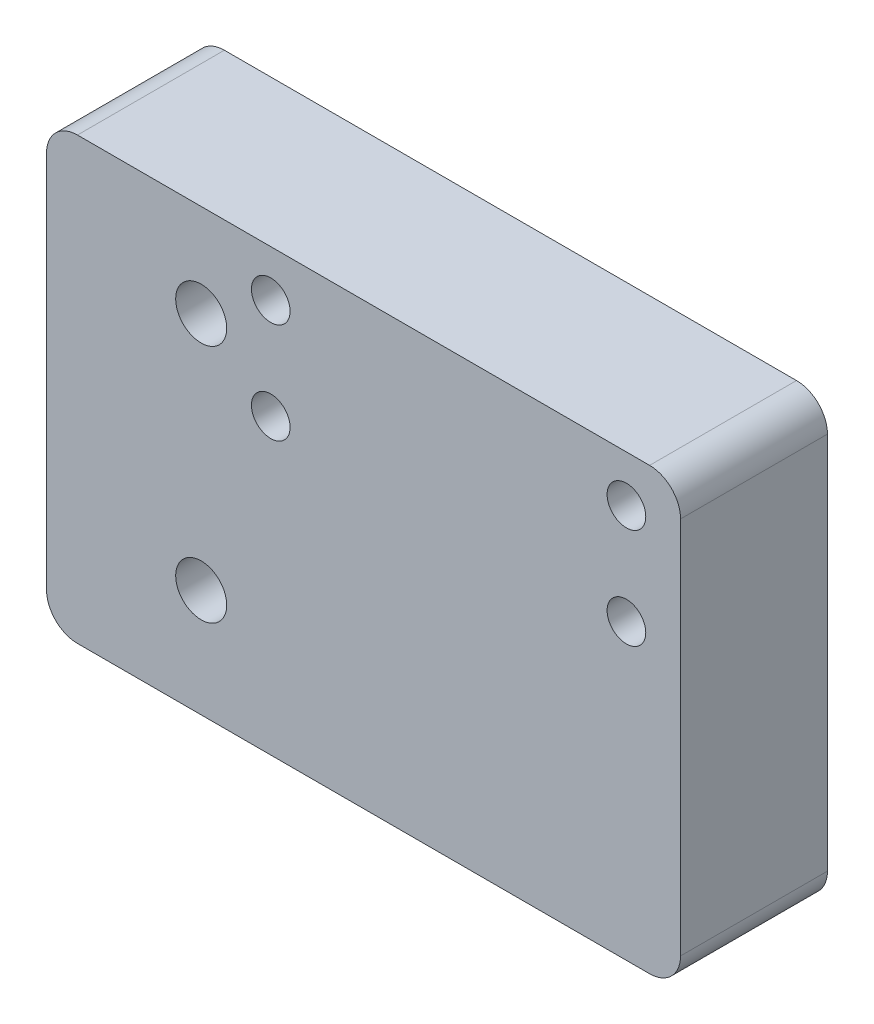
SolidWorks part; units mm, degrees
ref_plane "Front Plane" through (0, 0, 0) normal (0, 0, 1) x (1, 0, 0)
ref_plane "Top Plane" through (0, 0, 0) normal (0, 1, 0) x (1, 0, 0)
ref_plane "Right Plane" through (0, 0, 0) normal (1, 0, 0) x (0, 0, -1)
sketch "Sketch1" plane through (0, 0, 0) normal (0, 0, 1) x (1, 0, 0)
  line L1 (62, 68.7452) -> (-20, 68.7452)
  line L2 (62, 68.7452) -> (62, 8.7452)
  line L3 (62, 8.7452) -> (-20, 8.7452)
  line L4 (-20, 68.7452) -> (-20, 8.7452)
  dimension "D1" = 60
extrude "Boss-Extrude1" add sketch "Sketch1" along normal blind 19
hole_wizard "Tap Drill for M6 Tap1" positions "Sketch4" profile "Sketch3" hole size "M6" standard "ISO" end condition through all
sketch "Sketch4" plane through (0, 0, 19) normal (0, 0, 1) x (1, 0, 0)
  point P0 (9, 58.7452)
  point P3 (55, 58.7452)
  point P6 (55, 58.7452)
  point P9 (9, 58.7452)
  point P13 (55, 45.7452)
  point P15 (9, 45.7452)
sketch "Sketch3" plane through (9, 58.7452, 19) normal (1, 0, 0) x (0, -1, 0)
  line L0 (0, 0) -> (0, 19)
  line L1 (0, 19) -> (2.5, 19)
  line L2 (2.5, 19) -> (2.5, 0)
  line L5 (2.5, 0) -> (0, 0)
  line L11 (0, -6.35) -> (0, 107.95) construction
  dimension "Thru Hole Dia." = 5
  dimension "Thru Hole Depth" = 19
hole_wizard "CSK for M6 Countersunk Flat Head Screw1" positions "Sketch5" profile "Sketch6" countersink size "M6" standard "ISO" end condition through all
sketch "Sketch5" plane through (0, 0, 0) normal (0, 0, 1) x (1, 0, 0)
  line L0 (-20, 8.7452) -> (62, 8.7452) construction
  point P0 (0, 21.7452)
  point P2 (0, 52.7452)
  dimension "D1" = 31
  dimension "D2" = 13
sketch "Sketch6" plane through (0, 21.7452, 0) normal (1, 0, 0) x (0, 1, 0)
  line L0 (0, 0) -> (0, 19)
  line L1 (0, 19) -> (3.3, 19)
  line L2 (3.3, 19) -> (3.3, 3)
  line L3 (3.3, 3) -> (6.3, 0)
  line L5 (6.3, 0) -> (0, 0)
  line L6 (-3.3, 3) -> (-6.3, 0) construction
  line L11 (0, -6.35) -> (0, 107.95) construction
  dimension "Thru Hole Dia." = 6.6
  dimension "Thru Hole Depth" = 19
  dimension "Near C'Sink Dia." = 12.6
  dimension "Near C'Sink Angle" = 90
sketch "Sketch7" plane through (0, 0, 0) normal (0, 0, -1) x (-1, 0, 0)
  line L0 (20, 68.7452) -> (20, 8.7452) construction
  line L1 (20, 68.7452) -> (-62, 68.7452)
  line L2 (20, 68.7452) -> (20, 64.7452)
  line L3 (20, 64.7452) -> (-62, 64.7452)
  line L4 (-62, 68.7452) -> (-62, 64.7452)
  line L5 (-62, 8.7452) -> (-62, 68.7452) construction
extrude "Cut-Extrude1" cut sketch "Sketch7" against normal through all
sketch "Sketch10" plane through (0, 0, 0) normal (0, 0, -1) x (-1, 0, 0)
  line L1 (-62, 8.7452) -> (20, 8.7452)
  line L2 (-62, 8.7452) -> (-62, 7.7952)
  line L3 (-62, 7.7952) -> (20, 7.7952)
  line L4 (20, 8.7452) -> (20, 7.7952)
extrude "Boss-Extrude2" add sketch "Sketch10" against normal blind 19
fillet "Fillet1" radius 4 4 edges at (-20, 7.7952, 9.5) (62, 7.7952, 9.5) (-20, 64.7452, 9.5) (62, 64.7452, 9.5)
hole_wizard "Tap Drill for M5 Tap1" positions "Sketch8" profile "Sketch9" hole size "M5" standard "ISO"
sketch "Sketch8" plane through (0, 7.7952, 0) normal (0, -1, 0) x (-1, 0, 0)
  point P0 (-42, -9.5)
sketch "Sketch9" plane through (42, 7.7952, 9.5) normal (1, 0, 0) x (0, 0, -1)
  line L0 (0, 0) -> (0, 31.2618)
  line L1 (0, 31.2618) -> (2.1, 30)
  line L2 (2.1, 30) -> (2.1, 0)
  line L5 (2.1, 0) -> (0, 0)
  line L10 (0, 31.2618) -> (-2.1, 30) construction
  line L11 (0, -6.35) -> (0, 107.95) construction
  dimension "Hole Dia." = 4.2
  dimension "Hole Depth" = 30
  dimension "Drill Angle" = 118
